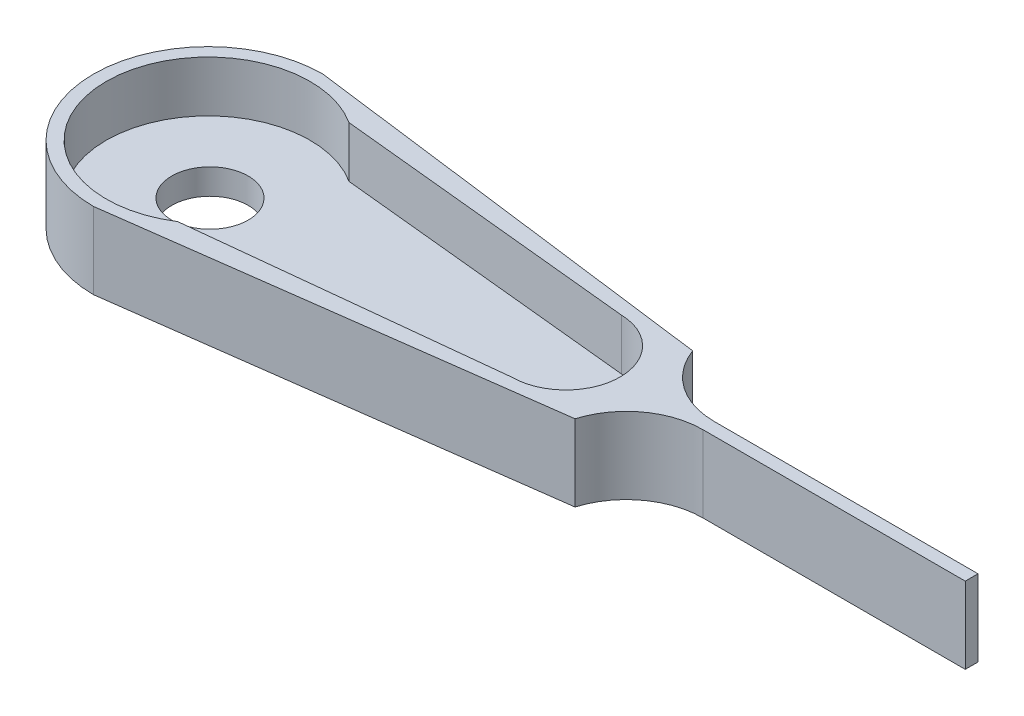
SolidWorks part; units mm, degrees
ref_plane "Front Plane" through (0, 0, 0) normal (0, 0, 1) x (1, 0, 0)
ref_plane "Top Plane" through (0, 0, 0) normal (0, 1, 0) x (1, 0, 0)
ref_plane "Right Plane" through (0, 0, 0) normal (1, 0, 0) x (0, 0, -1)
sketch "Sketch2" plane through (0, 0, 0) normal (0, 1, 0) x (1, 0, 0)
  line L0 (-24.822, 2.75) -> (-24.822, -2.75) construction
  line L1 (-26.9871, 0) -> (-9.8477, 0) construction
  line L2 (-10.3227, -0.2) -> (-10.3223, -2.339)
  line L3 (-10.3227, -0.2) -> (2.8515, -0.2)
  line L4 (-26.9871, 4.4282) -> (-10.3227, 2.279)
  line L5 (-26.9871, -4.5715) -> (-10.3223, -2.339)
  line L6 (-26.9871, 0) -> (-1.9871, 0) construction
  line L7 (-26.9871, -4.5715) -> (-2.3632, -1.0673) construction
  line L8 (-26.9871, 4.4282) -> (-10.3227, 2.3) construction
  line L9 (2.8515, -0.2) -> (2.8515, 0.3)
  line L11 (-24.8218, 3.2918) -> (-12.9398, 2.0943)
  line L12 (-12.9872, -2.1664) -> (-24.8217, -3.4351)
  line L13 (2.8515, 0.3) -> (-10.3227, 0.3)
  line L14 (-10.3227, 0.3) -> (-10.3227, 2.3)
  line L15 (-10.3227, 0.3) -> (-10.3227, -0.3836) construction
  circle A1 centre (-26.9871, 0) radius 1.5
  circle A3 centre (-26.9871, -0.0716) radius 4.4998
  circle A4 centre (-12.9872, -0.0358) radius 2.6366
  circle A6 centre (-12.9872, -0.0358) radius 2.1306
  circle A7 centre (-26.9871, -0.0716) radius 4.0002
  point P5 (0, 0)
  dimension "D1" = 5.5
  dimension "D2" = 0.5
  dimension "D3" = 14
  dimension "D4" = 14
  dimension "D7" = 0.3
  dimension "D5" = 2
  dimension "D9" = 0
  dimension "D10" = 0
  dimension "D8" = 29.8387
extrude "Boss-Extrude1" add sketch "Sketch2" along normal blind 1 contours A7 A1 | A7 L12 A3 L11 | A4 L11 A3 L12 | A6 L11 A4 L12 | A6 region at (-15.571, 0, 0.0394) region at (-19.2555, 0, 0.0535) region at (-24.3629, 0, 3.3143) region at (-12.9872, 0, 0.0358) region at (-30.8741, 0, 0.0717)
extrude "Boss-Extrude2" add sketch "Sketch2<3>" along normal blind 3 contours A7 L11 A3 L4 L5 L12 | A4 L12 A3 L5 | A4 L4 A3 L11 | A6 L12 A4 L11 | A4 L5 L2 L3 L9 L13 L14 L4 region at (-5.578, 0, -0.0313) region at (-19.5648, 0, 3.2424) region at (-13.495, 0, 2.5558) region at (-26.4106, 0, 4.3754) region at (-19.5963, 0, -3.1385)
sketch "Sketch2<3>" plane through (0, 0, 0) normal (0, 1, 0) x (1, 0, 0) same geometry as "Sketch2"
fillet "Fillet1" radius 3 2 edges at (-10.3227, 1.5, 0.2) (-10.3227, 1.5, -0.3)
fillet "Fillet2" radius 3 1 edges at (-10.3227, 1.5, 0.2)
